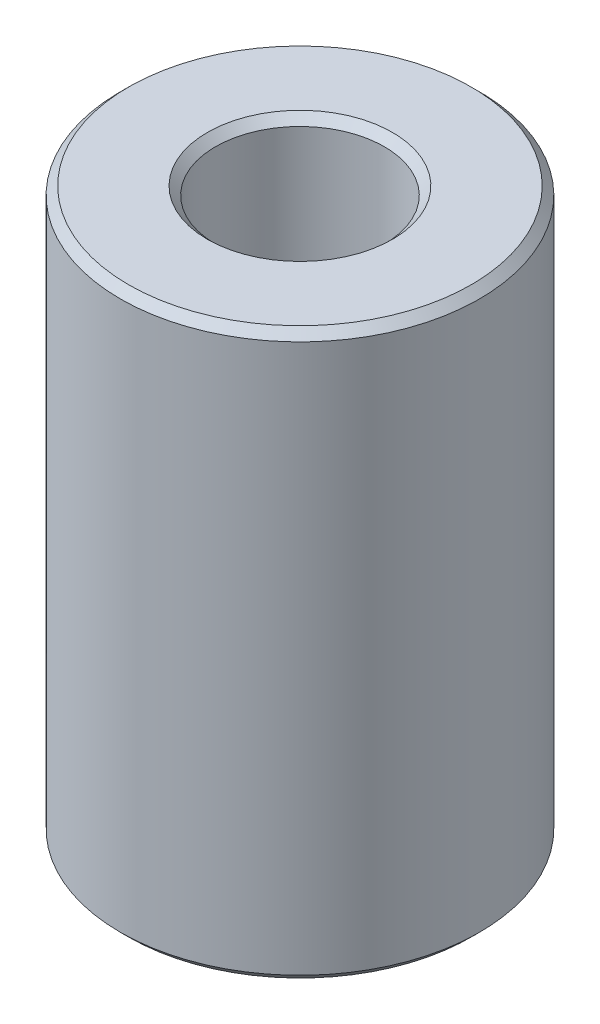
SolidWorks part; units mm, degrees
ref_plane "Front Plane" through (0, 0, 0) normal (0, 0, 1) x (1, 0, 0)
ref_plane "Top Plane" through (0, 0, 0) normal (0, 1, 0) x (1, 0, 0)
ref_plane "Right Plane" through (0, 0, 0) normal (1, 0, 0) x (0, 0, -1)
sketch "Sketch1" plane through (0, 0, 0) normal (0, 1, 0) x (1, 0, 0)
  circle A0 centre (0, 0) radius 47.5
  dimension "SLEEVE_OD" = 95
extrude "Boss-Extrude1" add sketch "Sketch1" along normal blind 149.481
sketch "Sketch2" plane through (0, 0, 0) normal (0, 1, 0) x (1, 0, 0)
  circle A0 centre (0, 0) radius 22.3306
  dimension "BORE_D" = 44.6612
extrude "Cut-Extrude1" cut sketch "Sketch2" along normal through all
chamfer "Chamfer1" distance 2.171 angle 45 4 edges at (0, 149.481, 22.3306) (0, 0, 22.3306) (0, 0, 47.5) (0, 149.481, 47.5)
